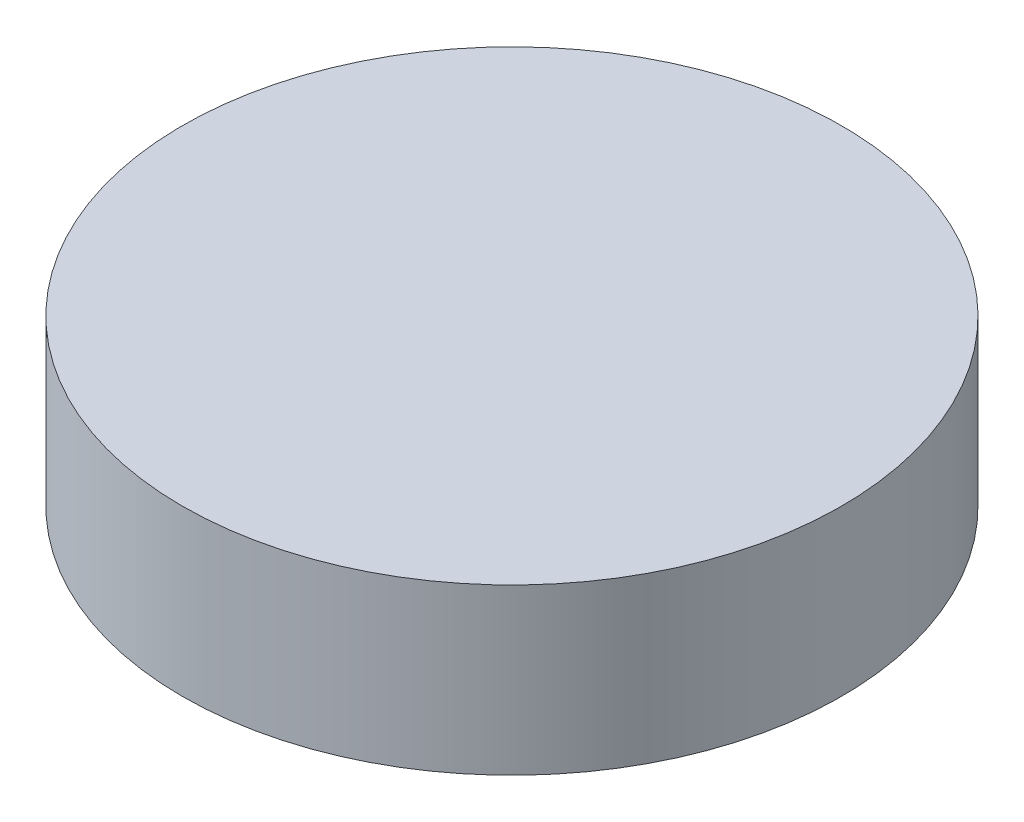
SolidWorks part; units mm, degrees
ref_plane "Front Plane" through (0, 0, 0) normal (0, 0, 1) x (1, 0, 0)
ref_plane "Top Plane" through (0, 0, 0) normal (0, 1, 0) x (1, 0, 0)
ref_plane "Right Plane" through (0, 0, 0) normal (1, 0, 0) x (0, 0, -1)
sketch "Sketch1" plane through (0, 0, 0) normal (0, 1, 0) x (1, 0, 0)
  circle A0 centre (0, 0) radius 25.4
  dimension "D1" = 50.8
extrude "Boss-Extrude1" add sketch "Sketch1" along normal blind 12.7
